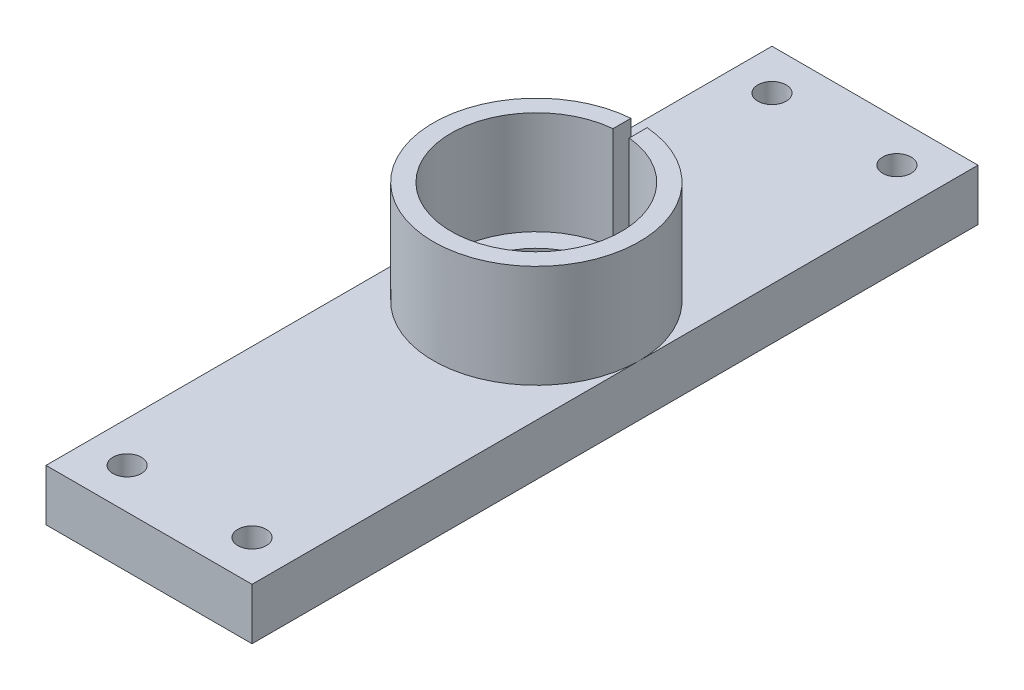
SolidWorks part; units mm, degrees
ref_plane "Front Plane" through (0, 0, 0) normal (0, 0, 1) x (1, 0, 0)
ref_plane "Top Plane" through (0, 0, 0) normal (0, 1, 0) x (1, 0, 0)
ref_plane "Right Plane" through (0, 0, 0) normal (1, 0, 0) x (0, 0, -1)
sketch "Sketch1" plane through (0, 0, 0) normal (0, 1, 0) x (1, 0, 0)
  line L1 (0, 0) -> (25.4, 0)
  line L2 (0, 0) -> (0, 89.5)
  line L3 (0, 89.5) -> (25.4, 89.5)
  line L4 (25.4, 0) -> (25.4, 89.5)
  circle A0 centre (5, 84.5) radius 1.75
  circle A1 centre (20.4, 84.5) radius 1.75
  circle A2 centre (5, 5) radius 1.75
  circle A3 centre (20.4, 5) radius 1.75
  dimension "D3" = 3.5
  dimension "D1" = 89.5
  dimension "D2" = 25.4
  dimension "D4" = 5
  dimension "D5" = 5
  dimension "D6" = 5
  dimension "D7" = 5
extrude "Boss-Extrude1" add sketch "Sketch1" along normal blind 6.35
sketch "Sketch2" plane through (0, 6.35, 0) normal (0, 1, 0) x (1, 0, 0)
  line L1 (25.4, 89.5) -> (0, 89.5) construction
  circle A0 centre (12.7, 47.75) radius 12.7
  circle A1 centre (12.7, 47.75) radius 10.5
  point P2 (12.7, 89.5)
  dimension "D1" = 41.75
  dimension "D2" = 25.4
  dimension "D3" = 21
extrude "Boss-Extrude2" add sketch "Sketch2" along normal blind 12.7
ref_plane "Plane1" through (0, 0, -35.05) normal (0, 0, 1) x (0, -1, 0)
sketch "Sketch5" plane through (0, 19.05, 0) normal (0, 1, 0) x (1, 0, 0)
  line L1 (11.7, 62.7043) -> (13.7, 62.7043)
  line L2 (11.7, 62.7043) -> (11.7, 54.6968)
  line L3 (11.7, 54.6968) -> (13.7, 54.6968)
  line L4 (13.7, 62.7043) -> (13.7, 54.6968)
  circle A0 centre (12.7, 47.75) radius 10.5 construction
  dimension "D1" = 1
  dimension "D2" = 2
extrude "Cut-Extrude1" cut sketch "Sketch5" against normal up to surface (12.7 mm away) up to face at (12.7, 6.35, -71.8)
sketch "Sketch6" plane through (0, 6.35, 0) normal (0, 1, 0) x (1, 0, 0)
  circle A0 centre (12.7, 47.75) radius 8
  dimension "D1" = 16
extrude "Cut-Extrude2" cut sketch "Sketch6" against normal blind 2.54
sketch "Sketch7" plane through (0, 3.81, 0) normal (0, 1, 0) x (1, 0, 0)
  circle A0 centre (12.7, 47.75) radius 2
  dimension "D1" = 4
extrude "Cut-Extrude3" cut sketch "Sketch7" against normal up to surface (3.81 mm away) up to face at (5, 0, -3.25)
